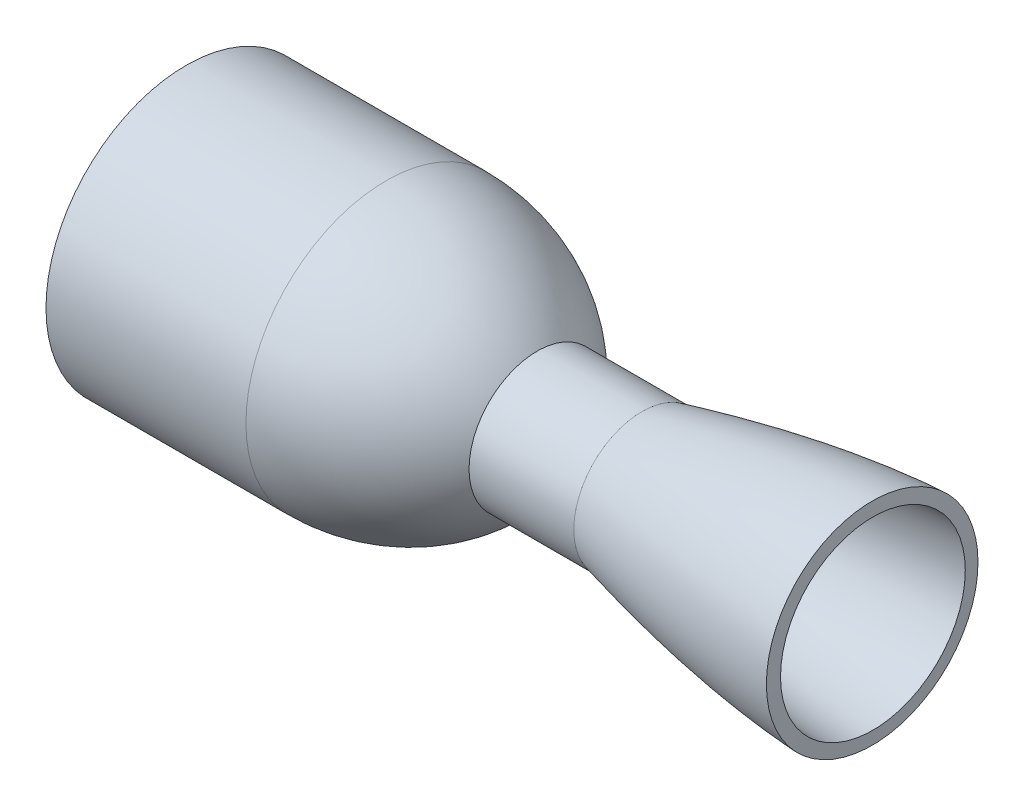
SolidWorks part; units mm, degrees
ref_plane "Front Plane"
ref_plane "Top Plane" through (0, 0, 0) normal (0, 1, 0) x (1, 0, 0)
ref_plane "Right Plane" through (0, 0, 0) normal (1, 0, 0) x (0, 0, -1)
sketch "Sketch1" plane through (0, 0, 0) normal (0, 0, 1) x (1, 0, 0)
  line L0 (0, 57.319) -> (85.97, 57.319)
  line L1 (142.7452, 19.05) -> (162.4462, 19.05) construction
  line L2 (162.5027, 23.8732) -> (-363.7553, 392.363) construction
  line L3 (202.4525, 22.2956) -> (290.9373, 46.005) construction
  line L4 (324.51, 43.655) -> (465.1357, 51.0249) construction
  line L5 (0, 0) -> (174.3765, 0) construction
  line L6 (160.6575, 26.05) -> (216.9371, 26.05)
  line L7 (0, 57.319) -> (0, 66.209)
  line L8 (0, 66.209) -> (94.4758, 66.209)
  line L9 (165.8892, 32.2101) -> (215.3957, 32.2101)
  line L10 (324.1777, 49.9963) -> (324.51, 43.655)
  arc A0 (85.97, 57.319) -> (160.6575, 26.05) centre (91.4096, -34.52) cw
  arc A1 (162.5027, 23.8732) -> (177.8, 19.05) centre (177.8, 45.72) ccw construction
  arc A2 (177.8, 19.05) -> (202.4525, 22.2956) centre (177.8, 114.3) ccw construction
  arc A3 (94.4758, 66.209) -> (165.8892, 32.2101) centre (94.4758, -25.791) cw
  parabola Q0 (216.9371, 26.05) -> (324.51, 43.655) focus (420.2156, -29.3912) apex (456.9181, 5.2587)
  spline S0 degree 1 poles (215.3957, 32.2101) (324.1777, 49.9963) knots 0 0 1 1 construction
  spline S1 degree 3 poles (215.3957, 32.2101) (217.915, 32.8405) (222.9886, 34.0856) (230.4404, 35.8402) (237.8044, 37.4995) (247.481, 39.5783) (259.3221, 41.9293) (273.1215, 44.3531) (286.5119, 46.3791) (299.4975, 48.0069) (309.9722, 49.0302) (318.1671, 49.6496) (322.1649, 49.8908) (324.1777, 49.9963) knots 0.493671 0.493671 0.493671 0.493671 0.493805 0.493939 0.494074 0.494208 0.494476 0.494745 0.495013 0.495282 0.495551 0.495685 0.495819 0.495819 0.495819 0.495819
  dimension "D5" = 92
  dimension "D6" = 26.67
  dimension "D7" = 95.25
  dimension "D1" = 35
  dimension "D2" = 57.319
  dimension "D3" = 85.97
  dimension "D4" = 177.8
  dimension "D8" = 19.05
  dimension "D10" = 3
  dimension "D11" = 43.655
  dimension "D12" = 146.71
  dimension "D9" = 15
  dimension "D13" = 7
  dimension "D14" = 8.89
  dimension "D15" = 6.35
revolve "Revolve1" add sketch "Sketch1" angle 360 about L5
equation "\"b\"= 35deg"
equation "\"D1@Sketch1\"=\"b\""
equation "\"Rc\"= 114.638 / 2mm"
equation "\"D2@Sketch1\"=\"Rc\""
equation "\"Lcyl\"= 85.97mm"
equation "\"D3@Sketch1\"=\"Lcyl\""
equation "\"Lc\"= 177.8mm"
equation "\"D4@Sketch1\"=\"Lc\""
equation "\"R2\"= 92mm"
equation "\"D5@Sketch1\"=\"R2\""
equation "\"R1\"= 26.67mm"
equation "\"Rn\"= 95.25mm"
equation "\"D7@Sketch1\"=\"Rn\""
equation "\"Rt\"= 38.1mm / 2"
equation "\"D8@Sketch1\"=\"Rt\""
equation "\"Tn\"= 15deg"
equation "\"Te\"= 3deg"
equation "\"D10@Sketch1\"=\"Te\""
equation "\"Re\"= 87.31mm / 2"
equation "\"D11@Sketch1\"=\"Re\""
equation "\"Le\"= 146.71mm"
equation "\"D12@Sketch1\"=\"Le\""
equation "\"D9@Sketch1\"=\"Tn\""
